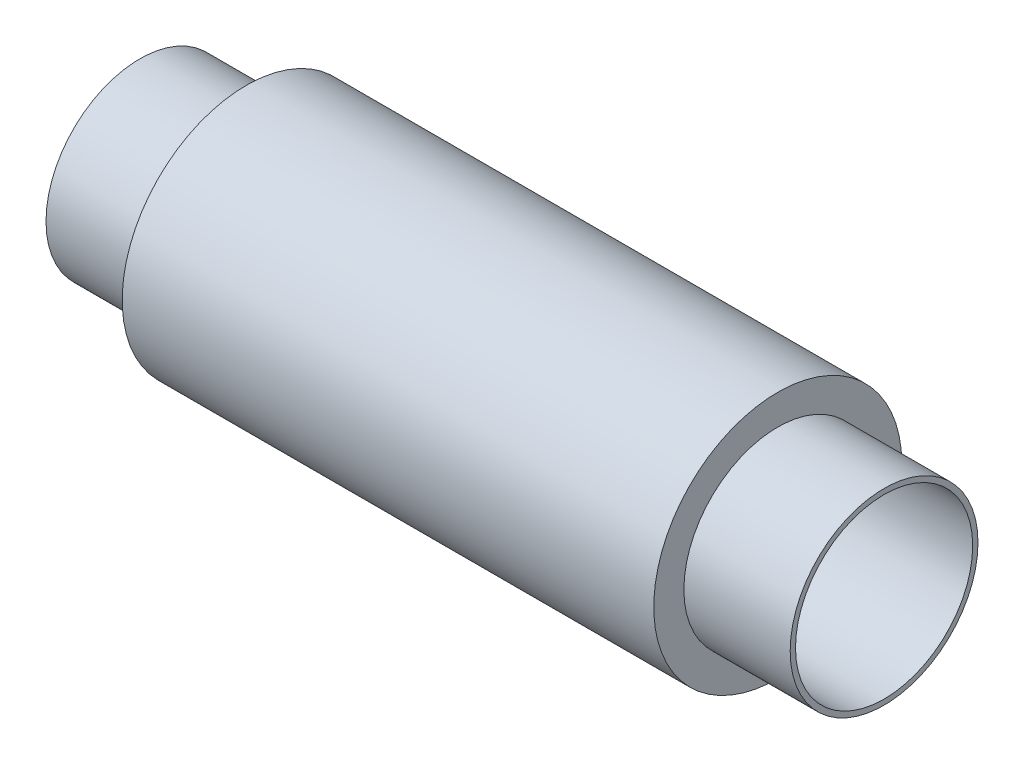
SolidWorks part; units mm, degrees
ref_plane "Front Plane" through (0, 0, 0) normal (0, 0, 1) x (1, 0, 0)
ref_plane "Top Plane" through (0, 0, 0) normal (0, 1, 0) x (1, 0, 0)
ref_plane "Right Plane" through (0, 0, 0) normal (1, 0, 0) x (0, 0, -1)
sketch "Sketch1" plane through (0, 0, 0) normal (1, 0, 0) x (0, 0, -1)
  line L0 (0, 5) -> (0, 7) construction
  circle A0 centre (0, 0) radius 5
  circle A1 centre (0, 0) radius 7
  dimension "D1" = 10
  dimension "D2" = 2
extrude "Boss-Extrude1" add sketch "Sketch1" along normal blind 30
sketch "Sketch2" plane through (0, 0, 0) normal (0, 0, 1) x (1, 0, 0)
  line L0 (0, 5) -> (-6, 5)
  line L1 (-6, 5) -> (-6, 5.3)
  line L2 (-6, 5.3) -> (0, 5.3)
  line L3 (0, 5.3) -> (0, 5)
  line L4 (15, 7) -> (15, -7) construction
  line L5 (30, 7) -> (0, 7) construction
  line L6 (0, -7) -> (30, -7) construction
  line L7 (30, 5.3) -> (30, 5)
  line L8 (36, 5.3) -> (30, 5.3)
  line L9 (36, 5) -> (36, 5.3)
  line L10 (30, 5) -> (36, 5)
  line L11 (-971, 0) -> (49029, 0) construction
  point P18 (15, 0)
  dimension "D1" = 6
  dimension "D2" = 0.3
revolve "Revolve1" add sketch "Sketch2" angle 360 about L11
